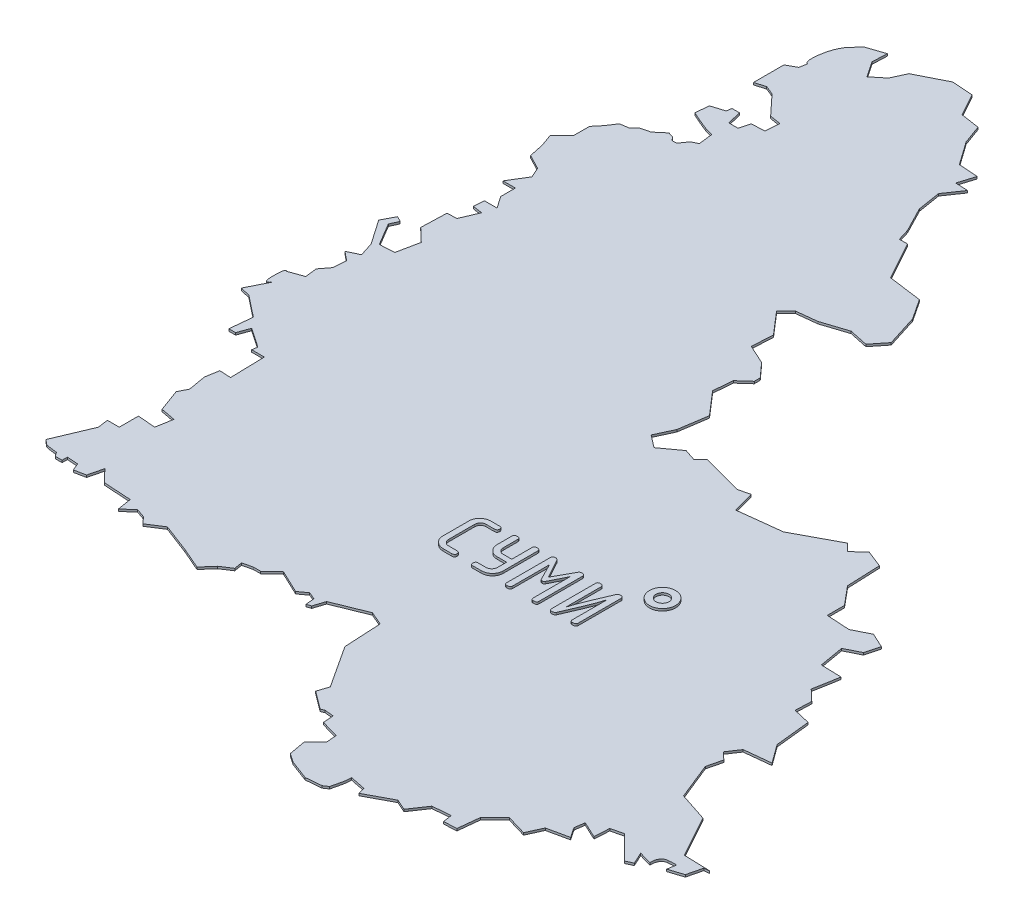
SolidWorks part; units mm, degrees
ref_plane "Спереди" through (0, 0, 0) normal (0, 0, 1) x (1, 0, 0)
ref_plane "Сверху" through (0, 0, 0) normal (0, 1, 0) x (1, 0, 0)
ref_plane "Справа" through (0, 0, 0) normal (1, 0, 0) x (0, 0, -1)
sketch "Эскиз1" plane through (0, 0, 0) normal (0, 1, 0) x (1, 0, 0)
  line B0 (889.5055, 7563.3402) -> (879.0991, 7572.4283)
  line B1 (879.0991, 7572.4283) -> (914.7937, 7657.4269)
  line B2 (914.7937, 7657.4269) -> (911.5831, 7681.4553)
  line B3 (911.5831, 7681.4553) -> (938.8145, 7681.4553)
  line B4 (938.8145, 7681.4553) -> (938.8145, 7725.5624)
  line B5 (938.8145, 7725.5624) -> (979.6882, 7722.3391)
  line B6 (979.6882, 7722.3391) -> (986.1804, 7759.9616)
  line B7 (986.1804, 7759.9616) -> (952.4136, 7766.4615)
  line B8 (952.4136, 7766.4615) -> (933.643, 7817.7085)
  line B9 (933.643, 7817.7085) -> (944.0037, 7838.4832)
  line B10 (944.0037, 7838.4832) -> (936.8536, 7879.3696)
  line B11 (936.8536, 7879.3696) -> (942.0682, 7909.875)
  line B12 (942.0682, 7909.875) -> (967.9965, 7908.5669)
  line B13 (967.9965, 7908.5669) -> (966.0636, 7988.3889)
  line B14 (966.0636, 7988.3889) -> (936.8536, 7988.3889)
  line B15 (936.8536, 7988.3889) -> (938.8145, 8000.7054)
  line B16 (938.8145, 8000.7054) -> (894.047, 8031.2057)
  line B17 (894.047, 8031.2057) -> (884.2807, 8003.9642)
  line B18 (884.2807, 8003.9642) -> (868.713, 8003.9642)
  line B19 (868.713, 8003.9642) -> (873.9099, 8055.2265)
  line B20 (873.9099, 8055.2265) -> (824.5932, 8094.157)
  line B21 (824.5932, 8094.157) -> (801.8932, 8099.3666)
  line B22 (801.8932, 8099.3666) -> (825.914, 8147.3777)
  line B23 (820.707, 8185.0052) -> (853.1454, 8196.6994)
  line B24 (853.1454, 8196.6994) -> (849.917, 8223.9485)
  line B25 (849.917, 8223.9485) -> (866.7699, 8246.0135)
  line B26 (866.7699, 8246.0135) -> (868.713, 8275.2108)
  line B27 (868.713, 8275.2108) -> (847.9739, 8292.0815)
  line B28 (847.9739, 8292.0815) -> (873.9099, 8304.4233)
  line B29 (873.9099, 8304.4233) -> (863.534, 8336.8566)
  line B30 (863.534, 8336.8566) -> (824.5932, 8393.3208)
  line B31 (824.5932, 8393.3208) -> (839.531, 8421.878)
  line B32 (839.531, 8421.878) -> (851.8957, 8415.3858)
  line B33 (851.8957, 8415.3858) -> (843.4146, 8396.5796)
  line B34 (843.4146, 8396.5796) -> (873.9099, 8345.297)
  line B35 (873.9099, 8345.297) -> (907.6436, 8347.2452)
  line B36 (907.6436, 8347.2452) -> (918.0576, 8397.8674)
  line B37 (918.0576, 8397.8674) -> (887.5522, 8427.0621)
  line B38 (887.5522, 8427.0621) -> (889.5055, 8485.472)
  line B39 (889.5055, 8485.472) -> (911.5831, 8486.7572)
  line B40 (911.5831, 8486.7572) -> (928.4437, 8526.3558)
  line B41 (928.4437, 8526.3558) -> (906.3584, 8529.6019)
  line B42 (906.3584, 8529.6019) -> (907.6436, 8553.6049)
  line B43 (907.6436, 8553.6049) -> (936.8536, 8553.6049)
  line B44 (936.8536, 8553.6049) -> (918.0576, 8580.8668)
  line B45 (918.0576, 8580.8668) -> (918.0576, 8614.6183)
  line B46 (918.0576, 8614.6183) -> (889.5055, 8614.6183)
  line B47 (889.5055, 8614.6183) -> (914.7937, 8656.1422)
  line B48 (914.7937, 8656.1422) -> (904.4051, 8679.495)
  line B49 (904.4051, 8679.495) -> (870.6739, 8697.0286)
  line B50 (870.6739, 8697.0286) -> (863.534, 8730.7623)
  line B51 (863.534, 8730.7623) -> (853.1454, 8759.9596)
  line B52 (853.1454, 8759.9596) -> (880.4046, 8787.2291)
  line B53 (880.4046, 8787.2291) -> (880.4046, 8822.9161)
  line B54 (880.4046, 8822.9161) -> (895.9875, 8841.7298)
  line B55 (895.9875, 8841.7298) -> (909.5791, 8862.4943)
  line B56 (909.5791, 8862.4943) -> (930.369, 8865.7481)
  line B57 (930.369, 8865.7481) -> (942.0682, 8877.427)
  line B58 (942.0682, 8877.427) -> (962.7895, 8882.6213)
  line B59 (962.7895, 8882.6213) -> (984.885, 8901.4249)
  line B60 (984.885, 8901.4249) -> (996.5944, 8898.1915)
  line B61 (996.5944, 8898.1915) -> (1003.7166, 8889.7562)
  line B62 (1003.7166, 8889.7562) -> (1014.0874, 8889.7562)
  line B63 (1014.0874, 8889.7562) -> (1027.7119, 8908.5826)
  line B64 (1027.7119, 8908.5826) -> (1041.3365, 8915.0723)
  line B65 (1041.3365, 8915.0723) -> (1037.4503, 8947.5132)
  line B66 (1037.4503, 8947.5132) -> (1018.6365, 8952.7202)
  line B67 (1018.6365, 8952.7202) -> (993.3203, 8963.0733)
  line B68 (993.3203, 8963.0733) -> (974.5243, 8971.5264)
  line B69 (974.5243, 8971.5264) -> (977.7451, 9002.0343)
  line B70 (977.7451, 9002.0343) -> (1006.9551, 9011.1047)
  line B71 (1006.9551, 9011.1047) -> (1008.888, 9022.7988)
  line B72 (1008.888, 9022.7988) -> (1025.7688, 9022.7988)
  line B73 (1025.7688, 9022.7988) -> (1034.2118, 8990.3427)
  line B74 (1034.2118, 8990.3427) -> (1054.9941, 8990.3427)
  line B75 (1054.9941, 8990.3427) -> (1061.4609, 9014.3381)
  line B76 (1061.4609, 9014.3381) -> (1091.9739, 9015.6462)
  line B77 (1091.9739, 9015.6462) -> (1093.917, 9048.0896)
  line B78 (1093.917, 9048.0896) -> (1068.6034, 9051.991)
  line B79 (1068.6034, 9051.991) -> (1025.7688, 9098.0717)
  line B80 (1025.7688, 9098.0717) -> (1004.9942, 9106.4994)
  line B81 (1004.9942, 9106.4994) -> (981.649, 9099.3722)
  line B82 (981.649, 9099.3722) -> (981.649, 9169.4533)
  line B83 (981.649, 9169.4533) -> (1003.7166, 9181.7749)
  line B84 (1003.7166, 9181.7749) -> (1006.9551, 9198.6583)
  line B85 (1017.3157, 9273.9388) -> (1037.4503, 9297.2941)
  line B86 (1037.4503, 9297.2941) -> (1078.3595, 9310.9237)
  line B87 (1078.3595, 9310.9237) -> (1077.021, 9277.1824)
  line B88 (1077.021, 9277.1824) -> (1101.0392, 9241.4903)
  line B89 (1101.0392, 9241.4903) -> (1128.3061, 9263.5527)
  line B90 (1128.3061, 9263.5527) -> (1143.2184, 9295.986)
  line B91 (1143.2184, 9295.986) -> (1210.0712, 9329.7426)
  line B92 (1210.0712, 9329.7426) -> (1258.095, 9326.4965)
  line B93 (1258.095, 9326.4965) -> (1286.6116, 9275.2215)
  line B94 (1286.6116, 9275.2215) -> (1329.4817, 9268.747)
  line B95 (1329.4817, 9268.747) -> (1345.0392, 9225.9175)
  line B96 (1345.0392, 9225.9175) -> (1382.6769, 9172.7096)
  line B97 (1382.6769, 9172.7096) -> (1426.8221, 9169.4533)
  line B98 (1426.8221, 9169.4533) -> (1415.1229, 9131.8182)
  line B99 (1415.1229, 9131.8182) -> (1443.6776, 9130.5101)
  line B100 (1443.6776, 9130.5101) -> (1416.4361, 9090.9318)
  line B101 (1416.4361, 9090.9318) -> (1424.8638, 9038.3614)
  line B102 (1424.8638, 9038.3614) -> (1454.0814, 8981.9074)
  line B103 (1454.0814, 8981.9074) -> (1462.5066, 8954.6455)
  line B104 (1462.5066, 8954.6455) -> (1481.3204, 8954.6455)
  line B105 (1481.3204, 8954.6455) -> (1529.3264, 8867.6912)
  line B106 (1529.3264, 8867.6912) -> (1605.8947, 8857.3254)
  line B107 (1605.8947, 8857.3254) -> (1636.4255, 8811.2422)
  line B108 (1636.4255, 8811.2422) -> (1659.1585, 8739.1977)
  line B109 (1659.1585, 8739.1977) -> (1633.159, 8706.7619)
  line B110 (1633.159, 8706.7619) -> (1590.3346, 8715.8424)
  line B111 (1590.3346, 8715.8424) -> (1532.6157, 8697.0286)
  line B112 (1532.6157, 8697.0286) -> (1486.5198, 8691.8317)
  line B113 (1486.5198, 8691.8317) -> (1464.4421, 8669.7591)
  line B114 (1464.4421, 8669.7591) -> (1508.5974, 8618.5121)
  line B115 (1508.5974, 8618.5121) -> (1505.3412, 8570.4756)
  line B116 (1505.3412, 8570.4756) -> (1549.4457, 8550.3715)
  line B117 (1549.4457, 8550.3715) -> (1578.671, 8517.9205)
  line B118 (1578.671, 8517.9205) -> (1578.671, 8504.2908)
  line B119 (1578.671, 8504.2908) -> (1553.3649, 8481.5832)
  line B120 (1553.3649, 8481.5832) -> (1549.4457, 8437.4533)
  line B121 (1549.4457, 8437.4533) -> (1595.534, 8384.2276)
  line B122 (1595.534, 8384.2276) -> (1585.8033, 8319.356)
  line B123 (1585.8033, 8319.356) -> (1566.9793, 8278.4594)
  line B124 (1566.9793, 8278.4594) -> (1595.534, 8256.4046)
  line B125 (1595.534, 8256.4046) -> (1638.366, 8287.5526)
  line B126 (1638.366, 8287.5526) -> (1665.6355, 8278.4594)
  line B127 (1665.6355, 8278.4594) -> (1681.2108, 8294.0373)
  line B128 (1681.2108, 8294.0373) -> (1774.6294, 8268.7312)
  line B129 (1774.6294, 8268.7312) -> (1800.5933, 8275.2108)
  line B130 (1800.5933, 8275.2108) -> (1814.2433, 8225.8916)
  line B131 (1814.2433, 8225.8916) -> (1912.8715, 8237.5705)
  line B132 (1912.8715, 8237.5705) -> (2008.9012, 8288.8379)
  line B133 (2008.9012, 8288.8379) -> (2025.7719, 8271.9799)
  line B134 (2025.7719, 8271.9799) -> (2051.7612, 8295.988)
  line B135 (2051.7612, 8295.988) -> (2090.6816, 8280.4127)
  line B136 (2090.6816, 8280.4127) -> (2093.9303, 8203.8317)
  line B137 (2093.9303, 8203.8317) -> (2129.6046, 8161.0022)
  line B138 (2129.6046, 8161.0022) -> (2129.6046, 8121.4239)
  line B139 (2129.6046, 8121.4239) -> (2182.8176, 8118.1804)
  line B140 (2182.8176, 8118.1804) -> (2220.4528, 8137.0043)
  line B141 (2220.4528, 8137.0043) -> (2254.1865, 8121.4239)
  line B142 (2254.1865, 8121.4239) -> (2245.7689, 8088.978)
  line B143 (2245.7689, 8088.978) -> (2212.0174, 8072.1022)
  line B144 (2212.0174, 8072.1022) -> (2221.7913, 8015.6329)
  line B145 (2221.7913, 8015.6329) -> (2268.4664, 8014.3401)
  line B146 (2268.4664, 8014.3401) -> (2258.0803, 7955.948)
  line B147 (2258.0803, 7955.948) -> (2283.4041, 7931.9298)
  line B148 (2283.4041, 7931.9298) -> (2282.0833, 7894.9423)
  line B149 (2282.0833, 7894.9423) -> (2321.0495, 7885.8491)
  line B150 (2321.0495, 7885.8491) -> (2329.4848, 7806.0372)
  line B151 (2329.4848, 7806.0372) -> (2360.6277, 7763.1976)
  line B152 (2360.6277, 7763.1976) -> (2300.2926, 7756.7231)
  line B153 (2300.2926, 7756.7231) -> (2282.0833, 7729.4664)
  line B154 (2282.0833, 7729.4664) -> (2298.9896, 7713.8936)
  line B155 (2298.9896, 7713.8936) -> (2290.5187, 7679.4893)
  line B156 (2290.5187, 7679.4893) -> (2324.3057, 7595.7836)
  line B157 (2324.3057, 7595.7836) -> (2391.1331, 7573.706)
  line B158 (2391.1331, 7573.706) -> (2443.6883, 7478.3239)
  line B159 (2443.6883, 7478.3239) -> (2503.3757, 7476.3808)
  line B160 (2503.3757, 7476.3808) -> (2504.059, 7475.7305)
  line B161 (2504.059, 7475.7305) -> (2491.7121, 7475.0854)
  line B162 (2491.7121, 7475.0854) -> (2483.3021, 7440.6887)
  line B163 (2483.3021, 7440.6887) -> (2450.846, 7430.2925)
  line B164 (2450.846, 7430.2925) -> (2454.0845, 7449.1291)
  line B165 (2418.3721, 7423.8129) -> (2389.1723, 7432.2483)
  line B166 (2389.1723, 7432.2483) -> (2401.5116, 7404.9992)
  line B167 (2401.5116, 7404.9992) -> (2385.9338, 7397.8618)
  line B168 (2385.9338, 7397.8618) -> (2331.4457, 7452.3752)
  line B169 (2331.4457, 7452.3752) -> (2304.1864, 7445.8779)
  line B170 (2304.1864, 7445.8779) -> (2302.2179, 7411.4863)
  line B171 (2302.2179, 7411.4863) -> (2264.5827, 7429.0022)
  line B172 (2264.5827, 7429.0022) -> (2261.3442, 7406.2869)
  line B173 (2261.3442, 7406.2869) -> (2276.9119, 7382.9291)
  line B174 (2276.9119, 7382.9291) -> (2228.9313, 7372.543)
  line B175 (2228.9313, 7372.543) -> (2213.3306, 7338.1413)
  line B176 (2213.3306, 7338.1413) -> (2167.2499, 7351.7785)
  line B177 (2167.2499, 7351.7785) -> (2133.4908, 7319.3326)
  line B178 (2133.4908, 7319.3326) -> (2128.2939, 7270.0083)
  line B179 (2128.2939, 7270.0083) -> (2099.1017, 7268.0652)
  line B180 (2099.1017, 7268.0652) -> (2095.8632, 7288.8399)
  line B181 (2095.8632, 7288.8399) -> (2054.9794, 7285.5887)
  line B182 (2054.9794, 7285.5887) -> (2032.8865, 7253.1453)
  line B183 (2032.8865, 7253.1453) -> (2028.378, 7247.3007)
  line B184 (2028.378, 7247.3007) -> (2003.7019, 7258.3345)
  line B185 (2003.7019, 7258.3345) -> (1945.3098, 7227.1738)
  line B186 (1945.3098, 7227.1738) -> (1940.7683, 7242.7465)
  line B187 (1897.9439, 7207.062) -> (1887.54, 7199.9297)
  line B188 (1887.54, 7199.9297) -> (1851.8454, 7196.7014)
  line B189 (1851.8454, 7196.7014) -> (1807.0779, 7213.5492)
  line B190 (1807.0779, 7213.5492) -> (1786.9865, 7227.1738)
  line B191 (1786.9865, 7227.1738) -> (1779.8466, 7266.7724)
  line B192 (1779.8466, 7266.7724) -> (1805.7647, 7292.0835)
  line B193 (1805.7647, 7292.0835) -> (1803.8318, 7316.0839)
  line B194 (1803.8318, 7316.0839) -> (1762.9657, 7327.7679)
  line B195 (1762.9657, 7327.7679) -> (1761.0049, 7351.7785)
  line B196 (1761.0049, 7351.7785) -> (1740.9058, 7353.7293)
  line B197 (1740.9058, 7353.7293) -> (1732.4273, 7350.4781)
  line B198 (1732.4273, 7350.4781) -> (1691.579, 7380.9885)
  line B199 (1691.579, 7380.9885) -> (1700.0245, 7406.2869)
  line B200 (1700.0245, 7406.2869) -> (1636.4255, 7503.6401)
  line B201 (1636.4255, 7503.6401) -> (1631.856, 7589.2939)
  line B202 (1631.856, 7589.2939) -> (1600.7309, 7602.9185)
  line B203 (1600.7309, 7602.9185) -> (1525.458, 7572.4283)
  line B204 (1525.458, 7572.4283) -> (1517.015, 7546.4645)
  line B205 (1517.015, 7546.4645) -> (1507.2665, 7543.2183)
  line B206 (1507.2665, 7543.2183) -> (1505.3412, 7563.3402)
  line B207 (1505.3412, 7563.3402) -> (1488.4349, 7570.4675)
  line B208 (1488.4349, 7570.4675) -> (1469.6211, 7556.848)
  line B209 (1469.6211, 7556.848) -> (1416.4361, 7582.1718)
  line B210 (1416.4361, 7582.1718) -> (1389.1692, 7556.848)
  line B211 (1389.1692, 7556.848) -> (1372.3163, 7556.848)
  line B212 (1372.3163, 7556.848) -> (1350.2564, 7551.6486)
  line B213 (1350.2564, 7551.6486) -> (1353.4771, 7532.8272)
  line B214 (1353.4771, 7532.8272) -> (1329.4817, 7517.257)
  line B215 (1329.4817, 7517.257) -> (1307.404, 7491.9535)
  line B216 (1307.404, 7491.9535) -> (1259.4082, 7512.7104)
  line B217 (1259.4082, 7512.7104) -> (1193.1828, 7538.0393)
  line B218 (1193.1828, 7538.0393) -> (1158.8115, 7515.9565)
  line B219 (1158.8115, 7515.9565) -> (1145.1869, 7530.8841)
  line B220 (1145.1869, 7530.8841) -> (1124.3945, 7538.0393)
  line B221 (1124.3945, 7538.0393) -> (1101.0392, 7517.257)
  line B222 (1101.0392, 7517.257) -> (1095.8424, 7549.7106)
  line B223 (1095.8424, 7549.7106) -> (1032.2611, 7553.5917)
  line B224 (1032.2611, 7553.5917) -> (1004.9942, 7582.1718)
  line B225 (1004.9942, 7582.1718) -> (996.5944, 7548.4076)
  line B226 (996.5944, 7548.4076) -> (971.2706, 7543.2183)
  line B227 (971.2706, 7543.2183) -> (964.1281, 7560.0712)
  line B228 (964.1281, 7560.0712) -> (938.8145, 7562.0372)
  line B229 (938.8145, 7562.0372) -> (938.8145, 7549.7106)
  line B230 (938.8145, 7549.7106) -> (923.2113, 7549.7106)
  line B231 (923.2113, 7549.7106) -> (916.7444, 7558.7936)
  line B232 (916.7444, 7558.7936) -> (893.4247, 7562.0372)
  line B233 (893.4247, 7562.0372) -> (889.5055, 7563.3402)
  spline B234 degree 2 poles (825.914, 8147.3777) (814.2249, 8130.5019) (814.2249, 8161.0022) knots 0.09465 0.09465 0.09465 0.098765 0.098765 0.098765
  spline B235 degree 2 poles (814.2249, 8161.0022) (814.2249, 8191.5076) (820.707, 8185.0052) knots 0.098765 0.098765 0.098765 0.102881 0.102881 0.102881
  spline B236 degree 2 poles (1006.9551, 9198.6583) (998.5019, 9200.5963) (1001.7735, 9227.8556) knots 0.358025 0.358025 0.358025 0.36214 0.36214 0.36214
  spline B237 degree 2 poles (1001.7735, 9227.8556) (1004.9942, 9255.1123) (1017.3157, 9273.9388) knots 0.36214 0.36214 0.36214 0.366255 0.366255 0.366255
  spline B238 degree 2 poles (2454.0845, 7449.1291) (2452.7815, 7451.0671) (2435.2529, 7449.1291) knots 0.695473 0.695473 0.695473 0.699588 0.699588 0.699588
  spline B239 degree 2 poles (2435.2529, 7449.1291) (2418.3721, 7447.8159) (2418.3721, 7423.8129) knots 0.699588 0.699588 0.699588 0.703704 0.703704 0.703704
  spline B240 degree 2 poles (1940.7683, 7242.7465) (1912.1079, 7248.1512) (1904.7056, 7250.0972) knots 0.794239 0.794239 0.794239 0.796872 0.796872 0.796872
  spline B241 degree 2 poles (1904.7056, 7250.0972) (1907.779, 7244.2411) (1897.9439, 7207.062) knots 0.799002 0.799002 0.799002 0.802469 0.802469 0.802469
sketch_block_instance "Блок21-1"
sketch_block "Блок21"
extrude "Бобышка-Вытянуть2" add sketch "Эскиз1" along normal blind 5 contours B240 B241 B186 B185 B184 B183 B182 B181 B180 B179 B178 B177 B176 B175 B174 B173 B172 B171 B170 B169 B168 B167 B166 B165 B239 B238 B164 B163 B162 B161 B160 B159 B158 B157 B156 B155 B154 B153 B152 B151 B150 B149 B148 B147 B146 B145 B144 B143 B142 B141 region at (1505.6963, 0, -8127.3776)
sketch "Эскиз2" plane through (0, 0, 0) normal (0, 1, 0) x (1, 0, 0)
  line L0 (1526.1172, 7807.069) -> (2122.6868, 7807.069) construction
  circle A0 centre (1910.2191, 7961.3329) radius 15
  circle A1 centre (1910.2191, 7961.3329) radius 30
  text T0 "<b>СУМИ</b>" font "GOST Type AU" height 110
  dimension "D1" = 30
  dimension "D2" = 60
extrude "Бобышка-Вытянуть3" add sketch "Эскиз2" along normal blind 10
scale "Масштаб1" scale about centroid uniform scaling yes scale factor 0.05
